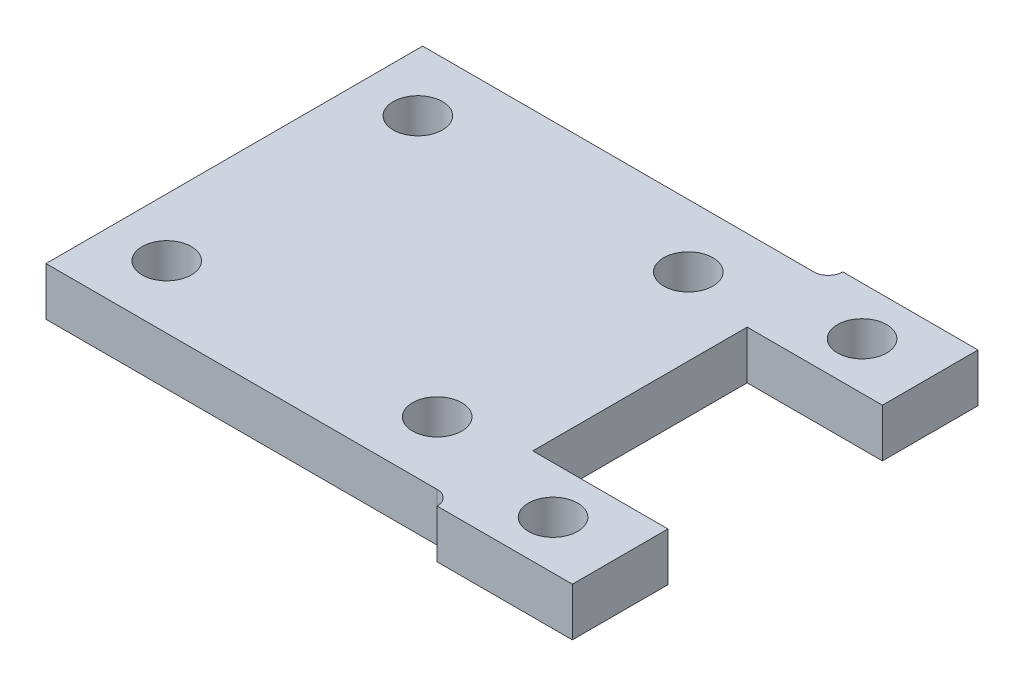
SolidWorks part; units mm, degrees
ref_plane "Front Plane" through (0, 0, 0) normal (0, 0, 1) x (1, 0, 0)
ref_plane "Top Plane" through (0, 0, 0) normal (0, 1, 0) x (1, 0, 0)
ref_plane "Right Plane" through (0, 0, 0) normal (1, 0, 0) x (0, 0, -1)
sketch "Sketch1" plane through (0, 0, 0) normal (0, 1, 0) x (1, 0, 0)
  line L0 (20, 19.5) -> (20, -19.5) construction
  line L1 (-20, -19.5) -> (20.5064, -19.5)
  line L2 (-20, -19.5) -> (-20, 19.5)
  line L3 (-20, 19.5) -> (20.5064, 19.5)
  line L4 (35.9964, -20.1332) -> (35.9964, -11.1)
  line L5 (21.9964, 0) -> (35.9964, 0) construction
  line L6 (35.9964, 11.1) -> (21.9964, 11.1)
  line L7 (21.9964, 19.5) -> (21.9964, -19.5) construction
  line L8 (20, 19.5) -> (-20, -19.5) construction
  line L9 (-20, 19.5) -> (20, -19.5) construction
  line L10 (0, 0) -> (0, 19.5) construction
  line L11 (0, 0) -> (-20, 0) construction
  line L12 (35.9964, 18.8668) -> (35.9964, 21)
  line L13 (35.9964, 21) -> (21.9964, 21)
  line L14 (21.9964, 21) -> (21.9964, 20.99)
  line L15 (21.9964, -20.99) -> (21.9964, -21)
  line L16 (21.9964, -21) -> (35.9964, -21)
  line L17 (35.9964, -21) -> (35.9964, -20.1332)
  line L18 (21.9964, 11.1) -> (21.9964, -11.1)
  line L19 (35.9964, -11.1) -> (21.9964, -11.1)
  line L20 (35.9964, 11.1) -> (35.9964, 18.8668)
  circle A0 centre (-14, 13) radius 2.55
  circle A1 centre (14, 13) radius 2.55
  circle A2 centre (14, -13) radius 2.55
  circle A3 centre (-14, -13) radius 2.55
  arc A4 (20.5064, 19.5) -> (21.9964, 20.99) centre (20.5064, 20.99) ccw
  arc A5 (20.5064, -19.5) -> (21.9964, -20.99) centre (20.5064, -20.99) cw
  circle A6 centre (28.9964, 16) radius 2.55
  circle A7 centre (28.9964, -16) radius 2.55
  point P0 (0, 0)
  point P29 (28.9964, 0)
  dimension "D5" = 5.1
  dimension "D12" = 1.49
  dimension "D13" = 1.49
  dimension "D14" = 5.1
  dimension "D1" = 56
  dimension "D2" = 39
  dimension "D3" = 40
  dimension "D4" = 14
  dimension "D6" = 6
  dimension "D7" = 6.5
  dimension "D8" = 1.5
  dimension "D9" = 1.5
  dimension "D10" = 55.9964
  dimension "D11" = 42
  dimension "D15" = 16
  dimension "D16" = 11.1
extrude "Boss-Extrude1" add sketch "Sketch1" along normal blind 5
